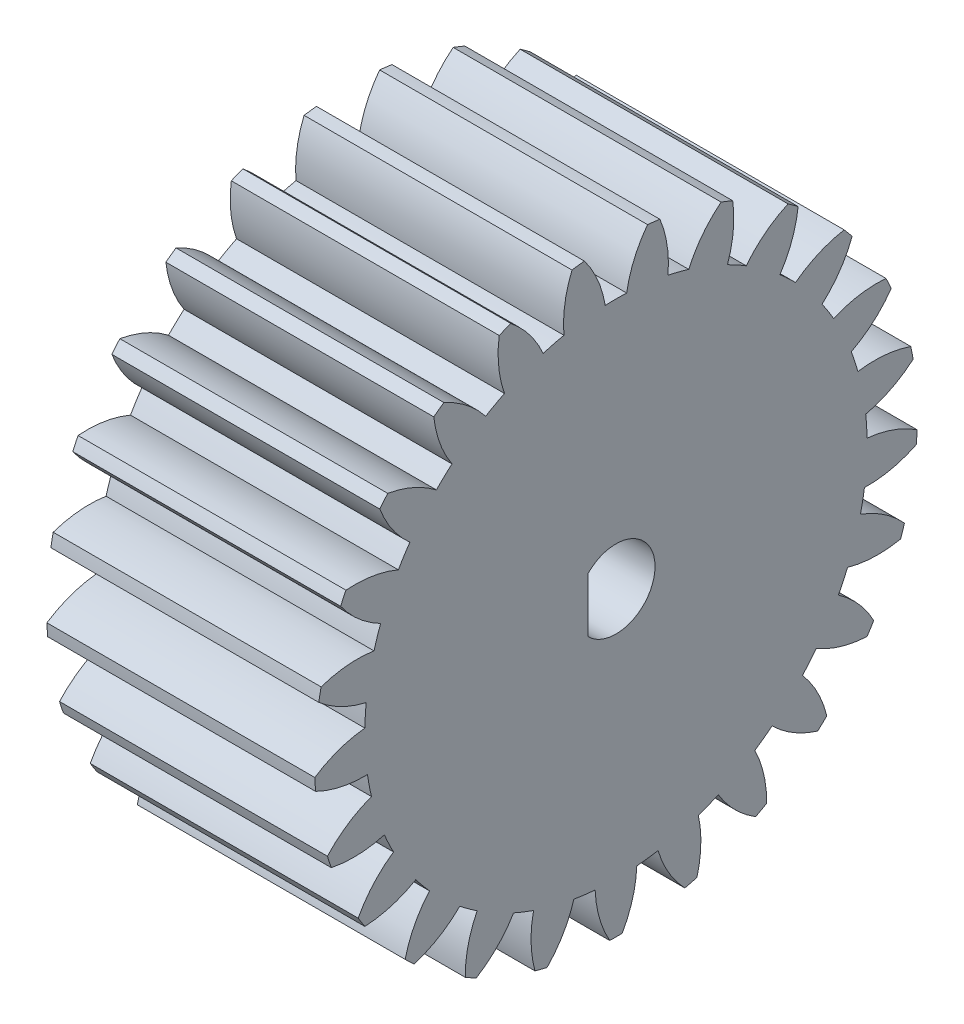
SolidWorks part; units mm, degrees
ref_plane "Plane1" through (0, 0, 0) normal (0, 0, 1) x (1, 0, 0)
ref_plane "Plane2" through (0, 0, 0) normal (0, 1, 0) x (1, 0, 0)
ref_plane "Plane3" through (0, 0, 0) normal (1, 0, 0) x (0, 0, -1)
sketch "HoldingSke" plane through (0, 0, 0) normal (0, 1, 0) x (1, 0, 0)
  line L0 (0, 0) -> (0.9063, -0.4226)
  line L1 (-15, 0) -> (100, 0) construction
  line L2 (0, 0) -> (-2.1039, 2.3779)
  line L3 (0, 0) -> (-11.863, 4.5341)
  line L4 (0, 0) -> (7.8269, 3.6497)
  line L5 (0, 0) -> (-46.8476, -17.4728)
  line L6 (0, 0) -> (-9.9476, -6.7116)
  line L7 (-2.1039, 2.3779) -> (8.6586, 51.2059)
  line L8 (-76.2, 54.61) -> (-75.7, 54.61)
  line L9 (-71.009, 38.7566) -> (-53.1078, 45.2721)
  line L10 (-76.2, 71.12) -> (104.1128, 71.12)
  line L11 (0, 0) -> (-12, 0)
  line L12 (-76.2, 101.6) -> (-76.162, 101.6)
  line L13 (24.9733, 27.94) -> (52.9518, 28.4284)
  line L14 (24.9733, 27.94) -> (24.9743, 27.94)
  line L15 (24.9733, 27.94) -> (100.4006, 29.5858)
  line L16 (-63.627, -1) -> (-12.827, -1)
  circle A0 centre (0, 0) radius 1.5
  circle A1 centre (0, 0) radius 11.249
  circle A2 centre (0, 0) radius 37.5
  circle A3 centre (0, 0) radius 1.5
  dimension "Num_teeth" = 25
  dimension "Pitch_radius" = 180.3128
  dimension "Width" = 12
  dimension "Thickness" = 12
sketch "BasProSke" plane through (0, 0, 0) normal (0, 1, 0) x (1, 0, 0)
  line L0 (-10, 0) -> (60, 0) construction
  line L1 (0, 0) -> (0, 13.5)
  line L2 (0, 0) -> (12, 0)
  line L3 (12, 0) -> (12, 13.5)
  line L4 (12, 13.5) -> (0, 13.5)
  dimension "Thickness" = 12
  dimension "Diameter" = 27
revolve "Base-Revolve" add sketch "BasProSke" angle 360 about L0
sketch "TooCutSke" plane through (0, 0, 0) normal (1, 0, 0) x (0, 0, -1)
  line L1 (0, 0) -> (0, 107) construction
  line L2 (0, 0) -> (-0.8514, 12.471) construction
  line L3 (0, 0) -> (-3.1282, 24.7619) construction
  line L4 (-0.8514, 12.471) -> (-1.5641, 12.3809) construction
  arc A0 (0.4801, 11.2388) -> (-0.4801, 11.2388) centre (0, 0) ccw
  arc A1 (1.4322, 13.4494) -> (-1.4322, 13.4494) centre (0, 0) ccw
  circle A2 centre (0, 0) radius 12.5 construction
  circle A3 centre (0, 0) radius 11.7462 construction
  arc A4 (-0.4801, 11.2388) -> (-1.4322, 13.4494) centre (-5.4133, 10.4244) ccw
  arc A5 (1.4322, 13.4494) -> (0.4801, 11.2388) centre (5.4133, 10.4244) ccw
extrude "ToothCut" cut sketch "TooCutSke" along normal through all
fillet "Breaks" [suppressed] radius 0.02 tangent propagation no
fillet "RootFillets" [suppressed] radius 0.251
pattern_circular "TeethCuts" count 25 every 14.4 about axis through (-10, 0, 0) along (1, 0, 0) of "ToothCut", "RootFillets", "Breaks"
sketch "HubNeaOneSke" plane through (0, 0, 0) normal (-1, 0, 0) x (0, 0, 1)
  circle A0 centre (0, 0) radius 11.249
  dimension "Diameter" = 22.498
extrude "HubNearOne" [suppressed] add sketch "HubNeaOneSke" along normal blind 38.0001
sketch "HubNeaBotSke" plane through (0, 0, 0) normal (-1, 0, 0) x (0, 0, 1)
  circle A0 centre (0, 0) radius 11.249
  dimension "Diameter" = 22.498
extrude "HubNearBoth" [suppressed] add sketch "HubNeaBotSke" along normal blind 19
ref_plane "FarPln" through (12, 0, 0) normal (1, 0, 0) x (0, 0, -1)
sketch "HubFarSke" plane through (12, 0, 0) normal (1, 0, 0) x (0, 0, -1)
  circle A0 centre (0, 0) radius 11.249
  dimension "Diameter" = 22.498
extrude "HubFar" [suppressed] add sketch "HubFarSke" along normal blind 19
sketch "BorSke" plane through (0, 0, 0) normal (1, 0, 0) x (0, 0, -1)
  circle A0 centre (0, 0) radius 1.5
  dimension "Diameter" = 3
extrude "Bore" cut sketch "BorSke" along normal mid plane 100.0001
sketch "KeySke" plane through (0, 0, 0) normal (1, 0, 0) x (0, 0, -1)
  line L0 (-0.6, 0) -> (-0.6, 2)
  line L1 (-0.6, 2) -> (0.6, 2)
  line L2 (0.6, 2) -> (0.6, 0)
  line L3 (0, 0) -> (0, 34) construction
  line L4 (-0.6, 0) -> (0.6, 0)
extrude "Keyway" [suppressed] cut sketch "KeySke" along normal mid plane 100.0001
pattern_circular "Keyway2" [suppressed] count 2 every 90 about axis through (-10, 0, 0) along (1, 0, 0) reverse direction yes
sketch "Sketch1" plane through (12, 0, 0) normal (1, 0, 0) x (0, 0, -1)
  line L0 (-1, 1.118) -> (-1, -1.118)
  line L1 (-1.25, 1.2247) -> (-1.25, -1.2247)
  circle A0 centre (0, 0) radius 1.5 construction
  arc A1 (-1, -1.118) -> (-1, 1.118) centre (0, 0) ccw
  arc A2 (-1.25, -1.2247) -> (-1.25, 1.2247) centre (0, 0) ccw
  circle A3 centre (0, 0) radius 1.5
  dimension "D1" = 1
  dimension "D2" = 0.25
extrude "Cut-Extrude1" cut sketch "Sketch1" against normal through all contours A3 A1 L1 A2 region at (12, 1.0118, 1.1691)
extrude "Boss-Extrude2" add sketch "Sketch1<4>" against normal through all contours L1 A3 region at (12, 0, 1.3508)
sketch "Sketch1<4>" plane through (12, 0, 0) normal (1, 0, 0) x (0, 0, -1) same geometry as "Sketch1"
sketch "Sketch2" plane through (12, 0, 0) normal (1, 0, 0) x (0, 0, -1)
  circle A0 centre (0, 0) radius 12.5 construction
  dimension "D1" = 25
equation "' \"Module@HoldingSke\" = 6.35"
equation "' \"Num_teeth@HoldingSke\" = 12"
equation "' \"Ap@HoldingSke\" =  20"
equation "' \"Ap@HoldingSke\" = 20"
equation "' \"Width@HoldingSke\" = 0.5 * 25.4"
equation "' \"Hub_dia@HoldingSke\"= 1 * 25.4"
equation "' \"Hub_dia@HoldingSke\" = 1 * 25.4"
equation "' \"Overall_len@HoldingSke\" = 1.0 * 25.4"
equation "' \"Bore@HoldingSke\" = 0.75 * 25.4"
equation "' \"T_dim@HoldingSke\" = 0.1 * 25.4"
equation "' \"Width@KeySke\" = 0.25 * 25.4"
equation "' \"Show_teeth@HoldingSke\" = 13"
equation "' \"Backlash@HoldingSke\" = 0.009 * 25.4"
equation "' \"Addendum_fac@HoldingSke\" = 1.0"
equation "' \"Dedendum_fac@HoldingSke\" = 1.25"
equation "' \"Dedendum_add@HoldingSke\" = 0.00005 * 25.4"
equation "' \"Clearance_fac@HoldingSke\" = 0.25"
equation "\"Pitch@HoldingSke\" = 1 / \"Module@HoldingSke\""
equation "\"Overcut_dia@TooCutSke\" = (\"Num_teeth@HoldingSke\" + 2 * \"Addendum_fac@HoldingSke\") / \"Pitch@HoldingSke\" + 0.002 * 25.4"
equation "\"Pitch_dia@TooCutSke\" = \"Num_teeth@HoldingSke\" / \"Pitch@HoldingSke\""
equation "\"Base_dia@TooCutSke\" = \"Num_teeth@HoldingSke\" / \"Pitch@HoldingSke\" * cos((\"Ap@HoldingSke\"  * 3.14159265 / 180))"
equation "\"Root_dia@TooCutSke\" = (\"Num_teeth@HoldingSke\" + 2) / \"Pitch@HoldingSke\" - 2 * (\"Addendum_fac@HoldingSke\" + \"Dedendum_fac@HoldingSke\") / \"Pitch@HoldingSke\" - \"Dedendum_add@HoldingSke\" * 2"
equation "\"Half_ang@TooCutSke\" = 180 / \"Num_teeth@HoldingSke\""
equation "\"Half_CT@TooCutSke\" = \"Num_teeth@HoldingSke\" / \"Pitch@HoldingSke\" * sin((3.14159265 / 2 / \"Num_teeth@HoldingSke\")) / 2 - 7 * \"Backlash@HoldingSke\" / 4"
equation "\"Flank_rad@TooCutSke\" = \"Num_teeth@HoldingSke\" / \"Pitch@HoldingSke\" / 5"
equation "\"Radius@RootFillets\" = \"Clearance_fac@HoldingSke\" / \"Pitch@HoldingSke\" + \"Dedendum_add@HoldingSke\""
equation "\"Break_rad@Breaks\" = 0.02 / \"Pitch@HoldingSke\""
equation "\"Thickness@HoldingSke\" = \"Width@HoldingSke\""
equation "\"OAL@HoldingSke\" = \"Thickness@HoldingSke\""
equation "\"MHD@HoldingSke\" = (\"Num_teeth@HoldingSke\" + 2) / \"Pitch@HoldingSke\" - 2 * (\"Addendum_fac@HoldingSke\" + \"Dedendum_fac@HoldingSke\")  / \"Pitch@HoldingSke\" - \"Dedendum_add@HoldingSke\" * 2"
equation "\"MBD@HoldingSke\" = (\"Num_teeth@HoldingSke\" + 2) / \"Pitch@HoldingSke\" - 2 * (\"Addendum_fac@HoldingSke\" + \"Dedendum_fac@HoldingSke\")  / \"Pitch@HoldingSke\" - \"Dedendum_add@HoldingSke\" * 2 - 0.002 * 25.4"
equation "\"MHD@HoldingSke\" = ((sgn( \"MHD@HoldingSke\" - \"Hub_dia@HoldingSke\" )-1)*( \"MHD@HoldingSke\" - \"Hub_dia@HoldingSke\" ))/-2+ \"Hub_dia@HoldingSke\""
equation "\"MBD@HoldingSke\" = ((sgn( \"MBD@HoldingSke\" - \"Bore@HoldingSke\" )-1)*( \"MBD@HoldingSke\" - \"Bore@HoldingSke\" ))/-2+ \"Bore@HoldingSke\""
equation "\"OAL@HoldingSke\" = ((sgn( \"OAL@HoldingSke\" - \"Overall_len@HoldingSke\" )+1)*( \"OAL@HoldingSke\" - \"Overall_len@HoldingSke\" ))/2 + \"Overall_len@HoldingSke\" + 0.000002 * 25.4"
equation "\"Num_teeth@TeethCuts\" = int( \"Show_teeth@HoldingSke\" ) + 1"
equation "\"Num_teeth@TeethCuts\" = ((sgn( \"Num_teeth@TeethCuts\" - \"Num_teeth@HoldingSke\" )-1)*( \"Num_teeth@TeethCuts\" - \"Num_teeth@HoldingSke\" ))/-2+ \"Num_teeth@HoldingSke\""
equation "\"Num_teeth@TeethCuts\" = ((sgn( \"Num_teeth@TeethCuts\" - 2.0)+1)*( \"Num_teeth@TeethCuts\" - 2.0))/2 +2.0"
equation "\"Angle@TeethCuts\" = 360.0 / \"Num_teeth@HoldingSke\""
equation "\"Diameter@BasProSke\" = (\"Num_teeth@HoldingSke\" + 2 * \"Addendum_fac@HoldingSke\") / \"Pitch@HoldingSke\""
equation "\"Thickness@BasProSke\"  = \"Thickness@HoldingSke\""
equation "' \"Fillet_rad@BasProSke\" =  \"Thickness@HoldingSke\" * 0.05"
equation "' \"Fillet_rad@BasProSke\" = \"Thickness@HoldingSke\" * 0.05"
equation "\"MHD@HoldingSke\" = ((sgn( \"MHD@HoldingSke\" - \"Root_dia@TooCutSke\" )-1)*( \"MHD@HoldingSke\" - \"Root_dia@TooCutSke\" ))/-2+ \"Root_dia@TooCutSke\""
equation "\"Diameter@HubNeaOneSke\" = \"MHD@HoldingSke\""
equation "\"Length@HubNearOne\" = \"OAL@HoldingSke\" - \"Thickness@BasProSke\""
equation "\"Diameter@HubNeaBotSke\" = \"MHD@HoldingSke\""
equation "\"Length@HubNearBoth\" = ( \"OAL@HoldingSke\" - \"Thickness@BasProSke\" ) / 2.0"
equation "\"Thickness@FarPln\" = \"Thickness@BasProSke\""
equation "\"Diameter@HubFarSke\" = \"MHD@HoldingSke\""
equation "\"Length@HubFar\" = ( \"OAL@HoldingSke\" - \"Thickness@BasProSke\" ) / 2.0"
equation "\"Diameter@BorSke\" = \"MBD@HoldingSke\""
equation "\"D1@Bore\" = \"OAL@HoldingSke\" * 2.0"
equation "\"D1@Keyway\" = \"OAL@HoldingSke\" * 2.0"
equation "\"Offset@KeySke\" = \"T_dim@HoldingSke\" + \"MBD@HoldingSke\" / 2.0"
